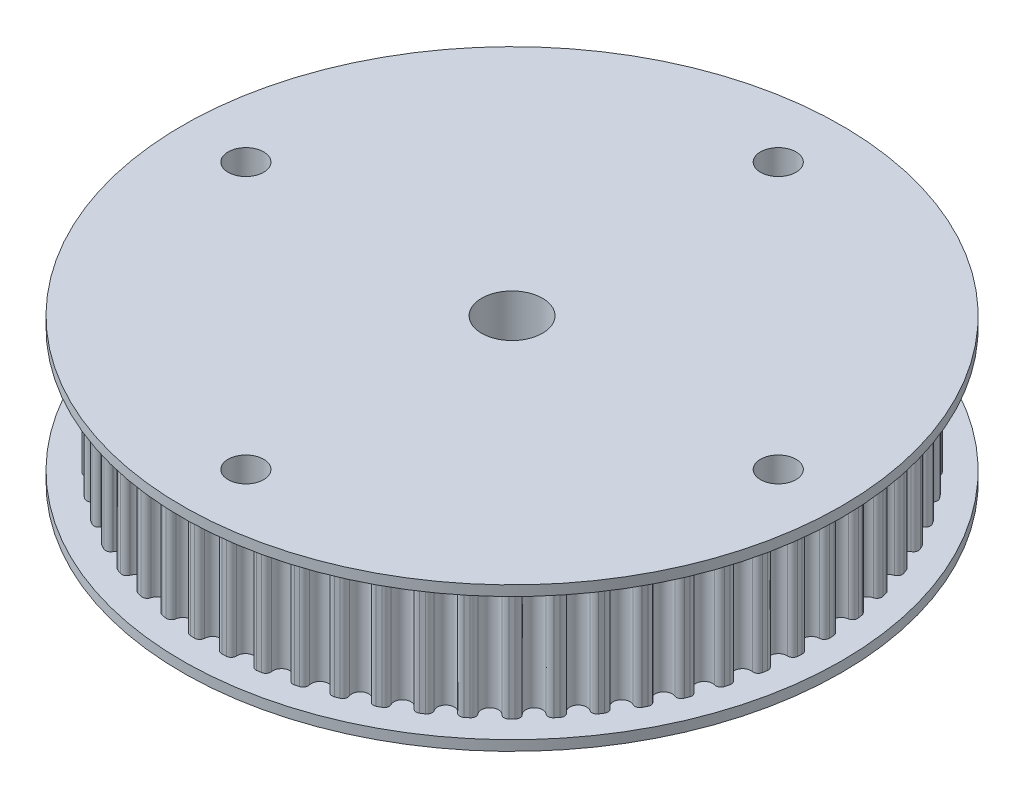
SolidWorks part; units mm, degrees
ref_plane "Front plan" through (0, 0, 0) normal (0, 0, 1) x (1, 0, 0)
ref_plane "Top plan" through (0, 0, 0) normal (0, 1, 0) x (1, 0, 0)
ref_plane "Right plan" through (0, 0, 0) normal (1, 0, 0) x (0, 0, -1)
sketch "Skica2" plane through (0, 0, 0) normal (0, 0, 1) x (1, 0, 0)
  line L1 (3, 7.112) -> (3, -7.112)
  line L3 (0, -9) -> (0, 9) construction
  line L7 (32.5, 6.112) -> (30, 6.112)
  line L8 (30, 6.112) -> (30, -6.112)
  line L9 (32.5, 6.112) -> (32.5, 7.112)
  line L12 (32.5, -7.112) -> (4, -7.112)
  line L13 (32.5, 7.112) -> (9, 7.112)
  line L14 (32.5, -7.112) -> (32.5, -6.112)
  line L15 (30, -6.112) -> (32.5, -6.112)
  line L17 (9, 7.112) -> (3, 7.112)
  line L18 (4, -7.112) -> (3, -7.112)
  point P0 (3, 0)
  point P7 (0, 0)
  dimension "D6" = 65
  dimension "D3" = 60
  dimension "D1" = 6
  dimension "D2" = 14.224
  dimension "D4" = 1
revolve "Revolute" add sketch "Skica2" angle 360 about L3 region at (16.6896, 0, 0)
sketch "Sketch2" plane through (0, 6.112, 0) normal (0, -1, 0) x (1, 0, 0)
  line L0 (0, 0) -> (0, 29.5189) construction
  line L1 (0, 0) -> (10.1159, 28.243) construction
  line L3 (0, 0) -> (-2.1349, 29.9239) construction
  circle A1 centre (0, 0) radius 28.6829 construction
  circle A2 centre (0, 0) radius 29.5 construction
  arc A3 (-0.8354, 29.4882) -> (0.8354, 29.4882) centre (0, 29.5189) ccw
  arc A7 (-1.3577, 29.9693) -> (-2.1349, 29.9239) centre (0, 0) ccw
  arc A8 (0, 31.4637) -> (2.1349, 29.9239) centre (0.5632, 29.9947) cw
  circle A9 centre (0, 0) radius 30 construction
  arc A10 (1.3577, 29.9693) -> (2.1349, 29.9239) centre (0, 0) cw
  arc A11 (1.3577, 29.9693) -> (0.8354, 29.4882) centre (1.3351, 29.4698) ccw
  arc A12 (0, 31.4637) -> (-2.1349, 29.9239) centre (-0.5632, 29.9947) ccw
  arc A13 (-1.3577, 29.9693) -> (-0.8354, 29.4882) centre (-1.3351, 29.4698) cw
  dimension "D2" = 1
  dimension "D4" = 0.836
  dimension "D6" = 60
  dimension "D3" = 1.5733
  dimension "D1" = 0.5
extrude "Cut-Extrude3" cut sketch "Sketch2" along normal up to surface (12.224 mm away) up to face at (32.5, -6.112, 0)
pattern_circular "CirPattern1" count 60 over 360 about axis through (0, -9, 0) along (0, -1, 0) of "Cut-Extrude3"
sketch "Sketch4" plane through (0, -7.112, 0) normal (0, -1, 0) x (1, 0, 0)
  circle A0 centre (0, 0) radius 20
  circle A1 centre (0, 0) radius 9.5
  dimension "D1" = 40
  dimension "D2" = 19
ref_plane "Plane1" through (0, -0.762, 0) normal (0, -1, 0) x (-1, 0, 0)
ref_plane "centre" through (0, -0.762, 0) normal (0, -1, 0) x (-1, 0, 0)
sketch "Esquisse1" plane through (0, -7.112, 0) normal (0, -1, 0) x (1, 0, 0)
  circle A0 centre (0, 0) radius 26.25
  dimension "D1" = 52.5
sketch "Esquisse2" plane through (0, -7.112, 0) normal (0, -1, 0) x (-1, 0, 0)
  circle A0 centre (-26.25, 0) radius 1.75
  circle A1 centre (0, 0) radius 26.25 construction
  circle A2 centre (0, 26.25) radius 1.75
  circle A3 centre (26.25, 0) radius 1.75
  circle A4 centre (0, -26.25) radius 1.75
  point P10 (0, 0)
  point P12 (0, 0)
  point P13 (0, 0)
  point P14 (-26.25, 0)
  dimension "D1" = 3.5
extrude "Enlèv. mat.-Extru.1" cut sketch "Esquisse2" against normal through all
equation "\"`\"=2"
equation "\"D6@Sketch2\"= \"D3@Skica2\""
